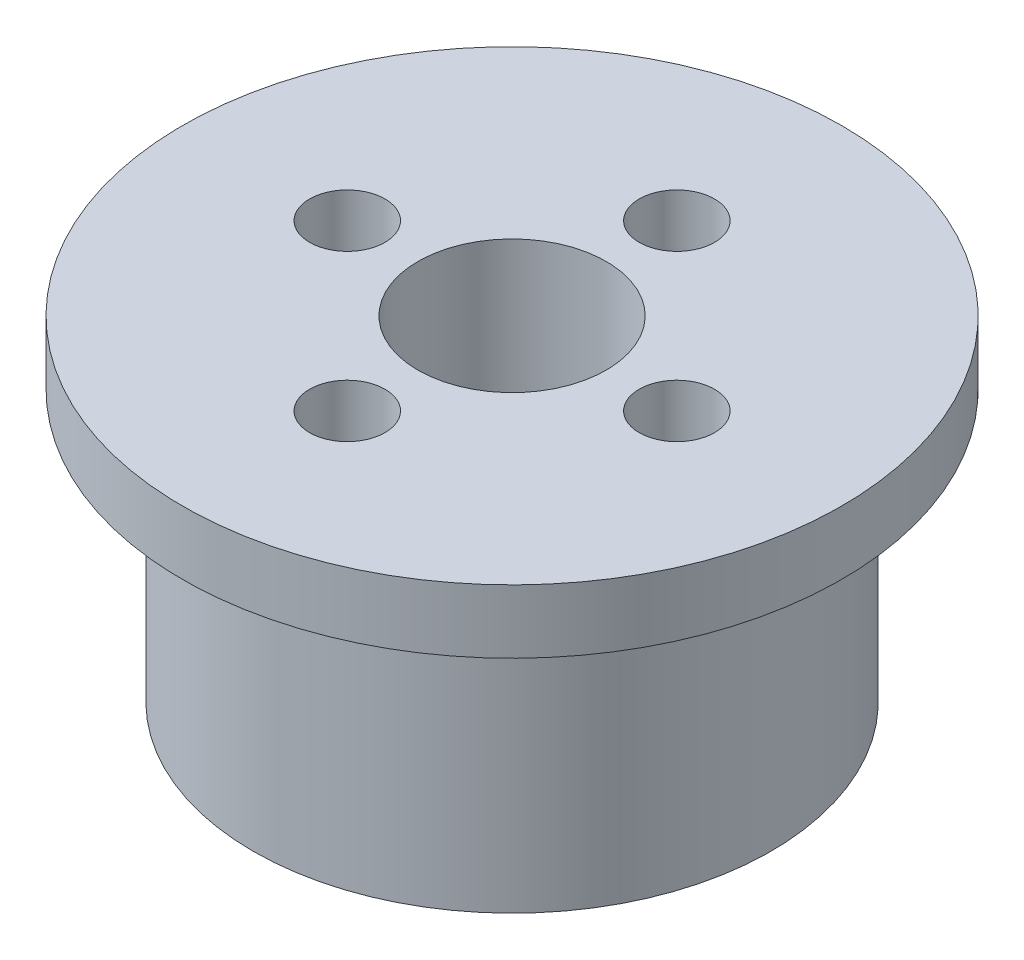
SolidWorks part; units mm, degrees
ref_plane "前视基准面" through (0, 0, 0) normal (0, 0, 1) x (1, 0, 0)
ref_plane "上视基准面" through (0, 0, 0) normal (0, 1, 0) x (1, 0, 0)
ref_plane "右视基准面" through (0, 0, 0) normal (1, 0, 0) x (0, 0, -1)
sketch "草图3" plane through (0, 0, 0) normal (0, 1, 0) x (1, 0, 0)
  circle A0 centre (0, 0) radius 11
  dimension "D1" = 22
extrude "凸台-拉伸1" add sketch "草图3" along normal blind 11.5
sketch "草图4" plane through (0, 11.5, 0) normal (0, 1, 0) x (1, 0, 0)
  circle A0 centre (0, 0) radius 14
  dimension "D1" = 28
extrude "凸台-拉伸2" add sketch "草图4" along normal blind 2.7
sketch "草图5" plane through (0, 14.2, 0) normal (0, 1, 0) x (1, 0, 0)
  line L0 (0, -14) -> (0, 14) construction
  line L1 (-4.65, 1.3568) -> (-7, 2.7135) construction
  line L2 (-1.3568, -4.65) -> (-2.7135, -7) construction
  line L3 (-2.7135, -7) -> (-1.3568, -9.35) construction
  line L4 (-1.3568, -9.35) -> (1.3568, -9.35) construction
  line L5 (1.3568, -9.35) -> (2.7135, -7) construction
  line L6 (2.7135, -7) -> (1.3568, -4.65) construction
  line L7 (1.3568, -4.65) -> (-1.3568, -4.65) construction
  line L8 (-7, 2.7135) -> (-9.35, 1.3568) construction
  line L9 (-9.35, 1.3568) -> (-9.35, -1.3568) construction
  line L10 (-9.35, -1.3568) -> (-7, -2.7135) construction
  line L11 (-7, -2.7135) -> (-4.65, -1.3568) construction
  line L12 (-4.65, -1.3568) -> (-4.65, 1.3568) construction
  line L13 (-14, 0) -> (14, 0) construction
  line L14 (1.3568, 4.65) -> (2.7135, 7) construction
  line L15 (2.7135, 7) -> (1.3568, 9.35) construction
  line L16 (1.3568, 9.35) -> (-1.3568, 9.35) construction
  line L17 (-1.3568, 9.35) -> (-2.7135, 7) construction
  line L18 (-2.7135, 7) -> (-1.3568, 4.65) construction
  line L19 (-1.3568, 4.65) -> (1.3568, 4.65) construction
  line L20 (0, 14) -> (0, -14) construction
  line L21 (4.65, -1.3568) -> (7, -2.7135) construction
  line L22 (7, -2.7135) -> (9.35, -1.3568) construction
  line L23 (9.35, -1.3568) -> (9.35, 1.3568) construction
  line L24 (9.35, 1.3568) -> (7, 2.7135) construction
  line L25 (7, 2.7135) -> (4.65, 1.3568) construction
  line L26 (4.65, 1.3568) -> (4.65, -1.3568) construction
  line L27 (14, 0) -> (-14, 0) construction
  circle A0 centre (0, 0) radius 4
  circle A1 centre (-7, 0) radius 2.35 construction
  circle A2 centre (0, 0) radius 14 construction
  circle A3 centre (0, -7) radius 2.35 construction
  circle A4 centre (0, 7) radius 2.35 construction
  circle A6 centre (7, 0) radius 2.35 construction
  circle A7 centre (0, 7) radius 1.6
  circle A8 centre (7, 0) radius 1.6
  circle A9 centre (0, -7) radius 1.6
  circle A10 centre (-7, 0) radius 1.6
  point P37 (0.1299, -0.075)
  point P43 (0, 0)
  point P45 (0, 0)
  point P51 (0, 0)
  point P56 (0, 0)
  dimension "D1" = 4
  dimension "D3" = 8
  dimension "D2" = 4.7
  dimension "D4" = 3.2
  dimension "D5" = 4
extrude "切除-拉伸1" cut sketch "草图5" against normal blind 50
